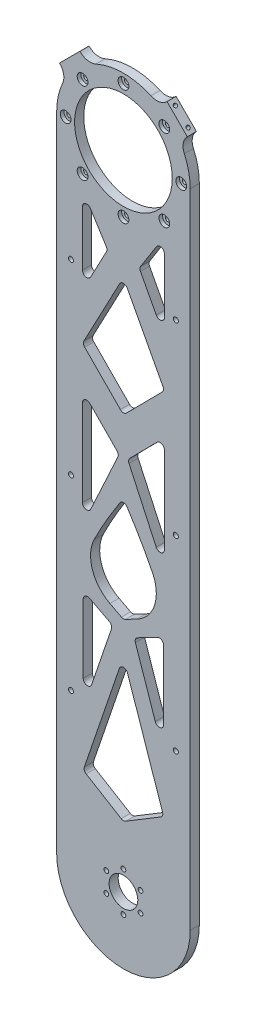
SolidWorks part; units mm, degrees
material "6061-T6 (SS)"
ref_plane "Front Plane" through (0, 0, 0) normal (0, 0, 1) x (1, 0, 0)
ref_plane "Top Plane" through (0, 0, 0) normal (0, 1, 0) x (1, 0, 0)
ref_plane "Right Plane" through (0, 0, 0) normal (1, 0, 0) x (0, 0, -1)
sketch "Sketch2" plane through (0, 0, 0) normal (0, 0, 1) x (1, 0, 0)
  line L0 (0, 0) -> (0, 500) construction
  line L1 (-46.5, 0) -> (-46.5, 500)
  line L2 (46.5, 0) -> (46.5, 500)
  arc A0 (-46.5, 0) -> (46.5, 0) centre (0, 0) ccw
  arc A1 (46.5, 500) -> (-46.5, 500) centre (0, 500) ccw
  circle A2 centre (0, 500) radius 37.25 construction
  circle A3 centre (0, 0) radius 10
  circle A4 centre (0, 13.75) radius 1.65
  circle A5 centre (0, 0) radius 13.75 construction
  circle A6 centre (11.9078, 6.875) radius 1.65
  circle A7 centre (11.9078, -6.875) radius 1.65
  circle A8 centre (0, -13.75) radius 1.65
  circle A9 centre (-11.9078, -6.875) radius 1.65
  circle A10 centre (-11.9078, 6.875) radius 1.65
  point P3 (0, 250)
  point P27 (0, 0)
  dimension "D2" = 74.5
  dimension "D4" = 20
  dimension "D5" = 3.3
  dimension "D6" = 27.5
  dimension "D3" = 46.5
  dimension "D1" = 500
  dimension "D7" = 6
extrude "Boss-Extrude1" add sketch "Sketch2" along normal blind 6.35
sketch "Sketch4" plane through (0, 0, 6.35) normal (0, 0, 1) x (1, 0, 0)
  line L0 (0, 500) -> (0, 999.1647) construction
  line L29 (46.5, 500) -> (-46.5, 500) construction
  line L31 (28.0053, 59.376) -> (0, 42.4117)
  line L32 (0, 141.6934) -> (28.0053, 59.376)
  line L33 (-28.0053, 59.376) -> (0, 141.6934)
  line L34 (0, 42.4117) -> (-28.0053, 59.376)
  line L35 (-7.5, 156.9059) -> (-28.0053, 96.6336)
  line L36 (-28.0053, 167.5829) -> (-7.5, 156.9059)
  line L37 (-28.0053, 96.6336) -> (-28.0053, 167.5829)
  line L38 (28.0053, 167.5829) -> (7.5, 156.9059)
  line L39 (28.0053, 96.6336) -> (28.0053, 167.5829)
  line L40 (7.5, 156.9059) -> (28.0053, 96.6336)
  line L41 (0, 164.2751) -> (28.5505, 179.1412)
  line L42 (0, 164.2751) -> (-28.5505, 179.1412)
  line L43 (28.5505, 259.5868) -> (3, 314.9383)
  line L44 (28.5505, 340.7931) -> (28.5505, 259.5868)
  line L45 (3, 314.9383) -> (28.5505, 340.7931)
  line L46 (-3, 314.9383) -> (-28.5505, 340.7931)
  line L47 (-28.5505, 259.5868) -> (-3, 314.9383)
  line L48 (-28.5505, 340.7931) -> (-28.5505, 259.5868)
  line L49 (0, 423.1428) -> (-28.5505, 369.2462)
  line L50 (-28.5505, 369.2462) -> (0, 340.3557)
  line L51 (0, 340.3557) -> (28.5505, 369.2462)
  line L52 (0, 423.1428) -> (28.5505, 369.2462)
  line L53 (-28.5505, 462.0952) -> (-28.5505, 401.2902)
  line L54 (-11, 434.4215) -> (-28.5505, 462.0952)
  line L55 (-28.5505, 401.2902) -> (-11, 434.4215)
  line L56 (28.5505, 401.2902) -> (11, 434.4215)
  line L57 (28.5505, 462.0952) -> (28.5505, 401.2902)
  line L58 (11, 434.4215) -> (28.5505, 462.0952)
  arc A0 (46.5, 500) -> (-46.5, 500) centre (0, 500) ccw construction
  arc A1 (46.5, 500) -> (-46.5, 500) centre (0, 500) ccw construction
  spline S2 degree 3 poles (28.5505, 179.1412) (45.3203, 216.9857) (19.4301, 259.7903) (0, 290.0258) knots 0 0 0 0 1 1 1 1
  spline S3 degree 3 poles (-28.5505, 179.1412) (-45.3203, 216.9857) (-19.4301, 259.7903) (0, 290.0258) knots 0 0 0 0 1 1 1 1
extrude "Cut-Extrude1" cut sketch "Sketch4" against normal blind 10
fillet "Fillet3" radius 3 30 edges at (-11, 434.4215, 3.175) (-28.5505, 401.2902, 3.175) (28.5505, 401.2902, 3.175) (11, 434.4215, 3.175) (28.5505, 462.0952, 3.175) (-28.5505, 462.0952, 3.175) (0, 423.1428, 3.175) (-28.5505, 369.2462, 3.175) (28.5505, 369.2462, 3.175) (0, 340.3557, 3.175) (28.5505, 340.7931, 3.175) (-28.5505, 340.7931, 3.175) (-3, 314.9383, 3.175) (3, 314.9383, 3.175) (28.5505, 259.5868, 3.175) (-28.5505, 259.5868, 3.175) (28.5505, 179.1412, 3.175) (0, 290.0258, 3.175) (-28.5505, 179.1412, 3.175) (0, 164.2751, 3.175) (-28.0053, 96.6336, 3.175) (28.0053, 96.6336, 3.175) (7.5, 156.9059, 3.175) (-28.0053, 167.5829, 3.175) (28.0053, 167.5829, 3.175) (0, 141.6934, 3.175) (28.0053, 59.376, 3.175) (-28.0053, 59.376, 3.175) (0, 42.4117, 3.175) (-7.5, 156.9059, 3.175)
sketch "Sketch5" plane through (0, 0, 6.35) normal (0, 0, 1) x (1, 0, 0)
  line L0 (0, -46.5) -> (108.8395, -46.5) construction
  line L1 (46.5, 100) -> (-46.5, 100) construction
  line L2 (46.5, 0) -> (46.5, 500) construction
  line L3 (-46.5, 500) -> (-46.5, 0) construction
  line L4 (-46.5, 106.35) -> (46.5, 106.35) construction
  line L5 (36.5, 106.35) -> (36.5, 100) construction
  line L6 (0, 106.35) -> (0, 100) construction
  line L7 (-46.5, 256.35) -> (46.5, 256.35) construction
  line L8 (-46.5, 181.35) -> (46.5, 181.35) construction
  line L9 (-46.5, 337.7) -> (46.5, 337.7) construction
  arc A1 (-46.5, 0) -> (46.5, 0) centre (0, 0) ccw construction
  circle A2 centre (36.5, 103.175) radius 1.75
  circle A3 centre (-36.5, 103.175) radius 1.75
  circle A4 centre (36.5, 259.525) radius 1.75
  circle A5 centre (-36.5, 259.525) radius 1.75
  circle A6 centre (36.5, 415.875) radius 1.75
  circle A7 centre (-36.5, 415.875) radius 1.75
  point P18 (36.5, 103.175)
  dimension "D2" = 3.5
  dimension "D1" = 146.5
  dimension "D3" = 10
  dimension "D4" = 6.35
  dimension "D5" = 150
  dimension "D6" = 81.35
  dimension "D7" = 81.35
extrude "Cut-Extrude2" cut sketch "Sketch5" against normal through all
sketch "Sketch6" plane through (0, 0, 6.35) normal (0, 0, 1) x (1, 0, 0)
  circle A0 centre (0, 500) radius 26.5
  arc A1 (46.5, 500) -> (-46.5, 500) centre (0, 500) ccw construction
  arc A2 (46.5, 500) -> (-46.5, 500) centre (0, 500) ccw construction
  dimension "D1" = 20
extrude "Cut-Extrude3" cut sketch "Sketch6" against normal blind 10
sketch "Sketch7" plane through (0, 0, 6.35) normal (0, 0, 1) x (1, 0, 0)
  line L1 (40.0163, 523.6842) -> (44.1104, 529.9682) construction
  line L2 (23.6842, 540.0163) -> (29.9682, 544.1104) construction
  line L3 (44.1104, 529.9682) -> (29.9682, 544.1104)
  line L4 (0, 500) -> (37.0393, 537.0393) construction
  line L5 (0, 500) -> (0, 546.5) construction
  arc A0 (46.5, 500) -> (-46.5, 500) centre (0, 500) ccw construction
  arc A1 (29.9682, 544.1104) -> (16.4747, 543.4837) centre (22.4977, 559.381) cw
  arc A2 (44.1104, 529.9682) -> (43.4837, 516.4747) centre (59.381, 522.4977) ccw
  arc A3 (16.4747, 543.4837) -> (43.4837, 516.4747) centre (0, 500) cw
  dimension "D3" = 17
  dimension "D5" = 17
  dimension "D1" = 20
  dimension "D2" = 7.5
  dimension "D4" = 8
  dimension "D6" = 8
  dimension "D7" = 45
extrude "Boss-Extrude2" add sketch "Sketch7" against normal up to surface (6.35 mm away) up to face at (26.5, 500, 0)
sketch "Sketch8" plane through (287.0393, 287.0393, 0) normal (0.7071, 0.7071, 0) x (0, 0, -1)
  line L0 (0, 363.5534) -> (-6.35, 363.5534) construction
  line L1 (0, 343.5534) -> (-6.35, 343.5534) construction
  line L2 (-6.35, 343.5534) -> (-6.35, 363.5534) construction
  point P0 (-3.175, 359.5534)
  point P1 (-3.175, 347.5534)
  dimension "D1" = 4
  dimension "D2" = 4
  dimension "D3" = 3.175
hole_wizard "Tap Drill for M3x0.5 Tap1" positions "Sketch8" profile "Sketch9" hole size "M3x0.5" standard "ANSI Metric"
sketch "Sketch9" plane through (32.7967, 541.282, 3.175) normal (0, 0, 1) x (-0.7071, 0.7071, 0)
  line L0 (0, 0) -> (0, 5.7511)
  line L1 (0, 5.7511) -> (1.25, 5)
  line L2 (1.25, 5) -> (1.25, 0)
  line L5 (1.25, 0) -> (0, 0)
  line L10 (0, 5.7511) -> (-1.25, 5) construction
  line L11 (0, -6.35) -> (0, 107.95) construction
  dimension "Hole Dia." = 2.5
  dimension "Hole Depth" = 5
  dimension "Drill Angle" = 118
pattern_circular "CirPattern2" count 2 every 90 about axis through (0, 500, -3.65) along (0, 0, 1) of "Boss-Extrude2", "Tap Drill for M3x0.5 Tap1"
sketch "Sketch10" plane through (0, 0, 6.35) normal (0, 0, 1) x (1, 0, 0)
  line L0 (-43.4837, 516.4747) -> (-63.4837, 516.4747)
  line L1 (43.4837, 516.4747) -> (63.4837, 516.4747)
  arc A0 (43.4837, 516.4747) -> (-43.4837, 516.4747) centre (0, 500) ccw
  arc A1 (46.5, 500) -> (43.4837, 516.4747) centre (0, 500) ccw construction
  arc A2 (-63.4837, 516.4747) -> (63.4837, 516.4747) centre (0, 500) cw
  dimension "D1" = 19.0866
  dimension "D2" = 20
extrude "Cut-Extrude4" cut sketch "Sketch10" against normal through all
sketch "Sketch11" plane through (0, 0, 6.35) normal (0, 0, 1) x (1, 0, 0)
  circle A0 centre (0, 500) radius 34
  circle A1 centre (0, 500) radius 26.5 construction
  dimension "D1" = 68
extrude "Cut-Extrude5" cut sketch "Sketch11" against normal through all
sketch "Sketch12" plane through (0, 0, 6.35) normal (0, 0, 1) x (1, 0, 0)
  line L0 (0, 534) -> (0, 546.5) construction
  circle A0 centre (0, 500) radius 40.25 construction
  circle A1 centre (0, 500) radius 34 construction
  circle A3 centre (0, 540.25) radius 1.75
  circle A4 centre (28.461, 528.461) radius 1.75
  circle A5 centre (40.25, 500) radius 1.75
  circle A6 centre (28.461, 471.539) radius 1.75
  circle A7 centre (0, 459.75) radius 1.75
  circle A8 centre (-28.461, 471.539) radius 1.75
  circle A9 centre (-40.25, 500) radius 1.75
  circle A10 centre (-28.461, 528.461) radius 1.75
  arc A11 (46.5, 500) -> (-46.5, 500) centre (0, 500) ccw construction
  point P4 (0, 540.25)
  point P36 (0, 500)
  dimension "D1" = 3.5
  dimension "D2" = 8
extrude "Cut-Extrude6" cut sketch "Sketch12" against normal through all both and the other way through all
sketch "Sketch13" plane through (0, 0, 0) normal (0, 0, -1) x (-1, 0, 0)
  line L0 (28.984, 180.1429) -> (28.984, 234.0954) construction
  line L1 (-28.984, 180.1429) -> (-28.984, 234.0954) construction
  line L2 (46.5, 234.0954) -> (-46.5, 234.0954)
  line L3 (46.5, 500) -> (46.5, 0) construction
  line L4 (-46.5, 0) -> (-46.5, 500) construction
  line L5 (46.5, 180.1429) -> (-46.5, 180.1429)
  line L6 (-46.5, 234.0954) -> (-46.5, 180.1429)
  line L7 (46.5, 234.0954) -> (46.5, 180.1429)
  spline S0 degree 3 poles (2.5314, 286.068) (21.3968, 256.4039) (44.1773, 216.1126) (28.984, 180.1429) knots 0.042883 0.042883 0.042883 0.042883 0.991187 0.991187 0.991187 0.991187 construction
  spline S1 degree 3 poles (-28.984, 180.1429) (-44.1773, 216.1126) (-21.3968, 256.4039) (-2.5314, 286.068) knots 0.008813 0.008813 0.008813 0.008813 0.957117 0.957117 0.957117 0.957117 construction
extrude "Cut-Extrude7" cut sketch "Sketch13" against normal through all
move or copy body "Body-Move/Copy1" bodies to move or copy 111 copy no translate (0, -52.7177, 0) parameters "D1"=0, "D2"=52.7177, "D3"=0
sketch "Sketch14" plane through (0, 180.1429, 0) normal (0, 1, 0) x (1, 0, 0)
  line L0 (-28.984, 0) -> (-46.5, 0) construction
  line L1 (-46.5, 0) -> (-46.5, -6.35) construction
  line L2 (-46.5, -6.35) -> (-28.984, -6.35) construction
  line L3 (-28.984, -6.35) -> (-28.984, 0) construction
  line L4 (28.984, -6.35) -> (46.5, -6.35) construction
  line L5 (46.5, -6.35) -> (46.5, 0) construction
  line L6 (46.5, 0) -> (28.984, 0) construction
  line L7 (28.984, 0) -> (28.984, -6.35) construction
  line L8 (-28.984, 0) -> (-46.5, 0)
  line L9 (-46.5, 0) -> (-46.5, -6.35)
  line L10 (-46.5, -6.35) -> (-28.984, -6.35)
  line L11 (-28.984, -6.35) -> (-28.984, 0)
  line L12 (28.984, -6.35) -> (46.5, -6.35)
  line L13 (46.5, -6.35) -> (46.5, 0)
  line L14 (46.5, 0) -> (28.984, 0)
  line L15 (28.984, 0) -> (28.984, -6.35)
extrude "Boss-Extrude3" add sketch "Sketch14" along normal up to surface (1.2348 mm away) up to face at (37.742, 181.3777, 3.175)
sketch "Sketch15" plane through (0, 0, 0) normal (0, 0, -1) x (-1, 0, 0)
  line L0 (-1.3855, 164.9966) -> (-27.606, 178.6494) construction
  line L1 (28.984, 181.3777) -> (28.984, 180.1429)
  line L2 (-28.984, 181.3777) -> (-28.984, 180.1429) construction
  line L3 (-9.4381, 169.1895) -> (-27.606, 178.6494)
  line L4 (-28.984, 181.3777) -> (-28.984, 180.1429)
  line L5 (0, 493.7823) -> (0, -46.5) construction
  line L6 (9.4381, 169.1895) -> (27.606, 178.6494)
  arc A0 (-20.3344, 202.3794) -> (-9.4381, 169.1895) centre (2.1078, 191.3636) ccw
  arc A1 (-28.984, 180.1429) -> (-27.606, 178.6494) centre (-26.2204, 181.3103) ccw construction
  arc A2 (-28.984, 180.1429) -> (-27.606, 178.6494) centre (-26.2204, 181.3103) ccw
  arc A3 (46.5, 447.2823) -> (-46.5, 447.2823) centre (0, 447.2823) ccw construction
  arc A4 (-46.5, 0) -> (46.5, 0) centre (0, 0) ccw construction
  arc A5 (28.984, 180.1429) -> (27.606, 178.6494) centre (26.2204, 181.3103) cw
  arc A6 (20.3344, 202.3794) -> (9.4381, 169.1895) centre (-2.1078, 191.3636) cw
  spline S0 degree 3 poles (1953.7087, 263.1445) (-2215.7642, -533.3919) (2154.4506, 1213.369) (-1849.5555, -532.5784) knots -2.670349 -2.670349 -2.670349 -2.670349 4.338748 4.338748 4.338748 4.338748 only from (-28.984, 181.3777) to (-2.5314, 233.3503) construction
  spline S1 degree 3 poles (28.984, 181.3777) (26.6659, 188.5284) (23.6788, 195.566) (20.3344, 202.3794) knots 0.47109 0.47109 0.47109 0.47109 0.656208 0.656208 0.656208 0.656208
  spline S2 degree 3 poles (-28.984, 181.3777) (-26.6659, 188.5284) (-23.6788, 195.566) (-20.3344, 202.3794) knots 0.47109 0.47109 0.47109 0.47109 0.656208 0.656208 0.656208 0.656208
  dimension "D1" = 25
  dimension "D2" = 540.2823
extrude "Boss-Extrude4" add sketch "Sketch15" against normal up to surface (6.35 mm away) up to face at (2.6453, 187.7844, 6.35)
sketch "Sketch16" plane through (0, 0, 0) normal (0, 0, -1) x (-1, 0, 0)
  line L0 (36.5, 103.175) -> (36.5, 363.1573) construction
  line L1 (-36.5, 103.175) -> (-36.5, 363.1573) construction
  circle A0 centre (-36.5, 363.1573) radius 1.75 construction
  circle A1 centre (36.5, 363.1573) radius 1.75 construction
  circle A2 centre (-36.5, 103.175) radius 1.75 construction
  circle A3 centre (36.5, 103.175) radius 1.75 construction
  circle A4 centre (-36.5, 363.1573) radius 1.75 construction
  circle A5 centre (36.5, 363.1573) radius 1.75 construction
  circle A6 centre (-36.5, 103.175) radius 1.75 construction
  circle A7 centre (36.5, 103.175) radius 1.75 construction
  circle A8 centre (36.5, 233.1662) radius 1.75
  circle A9 centre (-36.5, 233.1662) radius 1.75
  point P16 (36.5, 233.1662)
  point P18 (36.5, 233.1662)
extrude "Cut-Extrude8" cut sketch "Sketch16" against normal through all
sketch "Sketch17" plane through (0, 0, 0) normal (0, 0, -1) x (-1, 0, 0)
  circle A0 centre (36.5, 206.8073) radius 1.75 construction
  circle A1 centre (-36.5, 206.8073) radius 1.75 construction
  circle A2 centre (36.5, 206.8073) radius 1.75
  circle A3 centre (-36.5, 206.8073) radius 1.75
extrude "Boss-Extrude5" add sketch "Sketch17" against normal up to surface (6.35 mm away) up to face at (-34.75, 233.1662, 6.35)
sketch "Sketch18" plane through (0, 0, 0) normal (0, 0, -1) x (-1, 0, 0)
  line L0 (0, 447.2823) -> (0, 493.7823) construction
  line L1 (0, 447.2823) -> (32.8805, 480.1628) construction
  line L2 (-10, 492.6943) -> (-10, 500.1943) construction
  line L3 (25.0401, 486.4645) -> (30.3434, 491.7678)
  line L4 (30.3434, 491.7678) -> (44.4855, 477.6257)
  line L5 (44.4855, 477.6257) -> (39.1822, 472.3224)
  line L6 (25.0401, 486.4645) -> (39.1822, 472.3224)
  line L7 (-10, 500.1943) -> (10, 500.1943) construction
  line L8 (10, 500.1943) -> (10, 492.6943) construction
  line L9 (-10, 492.6943) -> (10, 492.6943) construction
  line L10 (-39.1822, 472.3224) -> (-44.4855, 477.6257)
  line L11 (-44.4855, 477.6257) -> (-30.3434, 491.7678)
  line L12 (-30.3434, 491.7678) -> (-25.0401, 486.4645)
  line L13 (-39.1822, 472.3224) -> (-25.0401, 486.4645)
  arc A0 (46.5, 447.2823) -> (-46.5, 447.2823) centre (0, 447.2823) ccw construction
  point P11 (32.1111, 479.3934)
  point P13 (0, 492.6943)
  dimension "D1" = 45
  dimension "D2" = 20
  dimension "D3" = 7.5
  dimension "D4" = 3
extrude "Boss-Extrude6" add sketch "Sketch18" against normal up to surface (6.35 mm away) up to face at (-34.75, 233.1662, 6.35)
sketch "Sketch20" plane through (-261.0556, 261.0556, 0) normal (-0.7071, 0.7071, 0) x (0, 0, 1)
  line L0 (6.35, 316.2764) -> (0, 316.2764) construction
  line L1 (6.35, 306.2764) -> (6.35, 326.2764) construction
  line L2 (0, 306.2764) -> (0, 326.2764) construction
  point P0 (3.175, 322.5264)
  point P9 (3.175, 316.2764)
  point P10 (3.175, 310.0264)
  dimension "D1" = 12.5
hole_wizard "M3x0.5 Tapped Hole1" positions "Sketch20" profile "Sketch21" tap size "M3x0.5" standard "ANSI Metric"
sketch "Sketch21" plane through (-32.995, 489.1162, 3.175) normal (0, 0, 1) x (-0.7071, -0.7071, 0)
  line L0 (0, 0) -> (0, 8.2511)
  line L1 (0, 8.2511) -> (1.25, 7.5)
  line L2 (1.25, 7.5) -> (1.25, 0)
  line L5 (1.25, 0) -> (0, 0)
  line L10 (0, 8.2511) -> (-1.25, 7.5) construction
  line L11 (0, -6.35) -> (0, 107.95) construction
  dimension "Tap Drill Dia." = 2.5
  dimension "Tap Drill Depth" = 7.5
  dimension "Drill Angle" = 118
cosmetic thread "Hole Thread1" parameters "D1"=6, "D2"=3
cosmetic thread "Hole Thread2" parameters "D1"=6, "D2"=3
pattern_circular "CirPattern3" count 2 over 90 about axis through (0, 447.2823, 0) along (0, 0, 1) of "M3x0.5 Tapped Hole1" reverse direction yes
cosmetic thread "Hole Thread5" parameters "D1"=6, "D2"=3
cosmetic thread "Hole Thread6" parameters "D1"=6, "D2"=3
cosmetic thread "Hole Thread7" parameters "D1"=6, "D2"=3
cosmetic thread "Hole Thread8" parameters "D1"=6, "D2"=3
fillet "Fillet4" radius 10 4 edges at (-39.1822, 472.3224, 3.175) (-25.0401, 486.4645, 3.175) (39.1822, 472.3224, 3.175) (25.0401, 486.4645, 3.175)
sketch "Sketch22" plane through (0, 0, 6.35) normal (0, 0, 1) x (1, 0, 0)
  circle A0 centre (0, 487.5323) radius 1.75 construction
  circle A1 centre (0, 487.5323) radius 1.75 construction
  circle A2 centre (0, 487.5323) radius 3.75
  dimension "D1" = 7.5
extrude "shallow_counterbore" cut sketch "Sketch22" against normal blind 2.5
pattern_circular "shallow_counterbore_2" count 8 over 360 about axis through (0, 447.2823, 0) along (0, 0, 1) of "shallow_counterbore"
equation "\"L1L\"=500"
equation "\"L1Thick\"=6.35"
equation "\"D1@Sketch2\"=\"L1L\""
equation "\"Harm-Drive-Outer\"=74.5"
equation "\"D2@Sketch2\"=\"Harm-Drive-Outer\""
equation "\"D1@Boss-Extrude1\"=\"L1Thick\""
